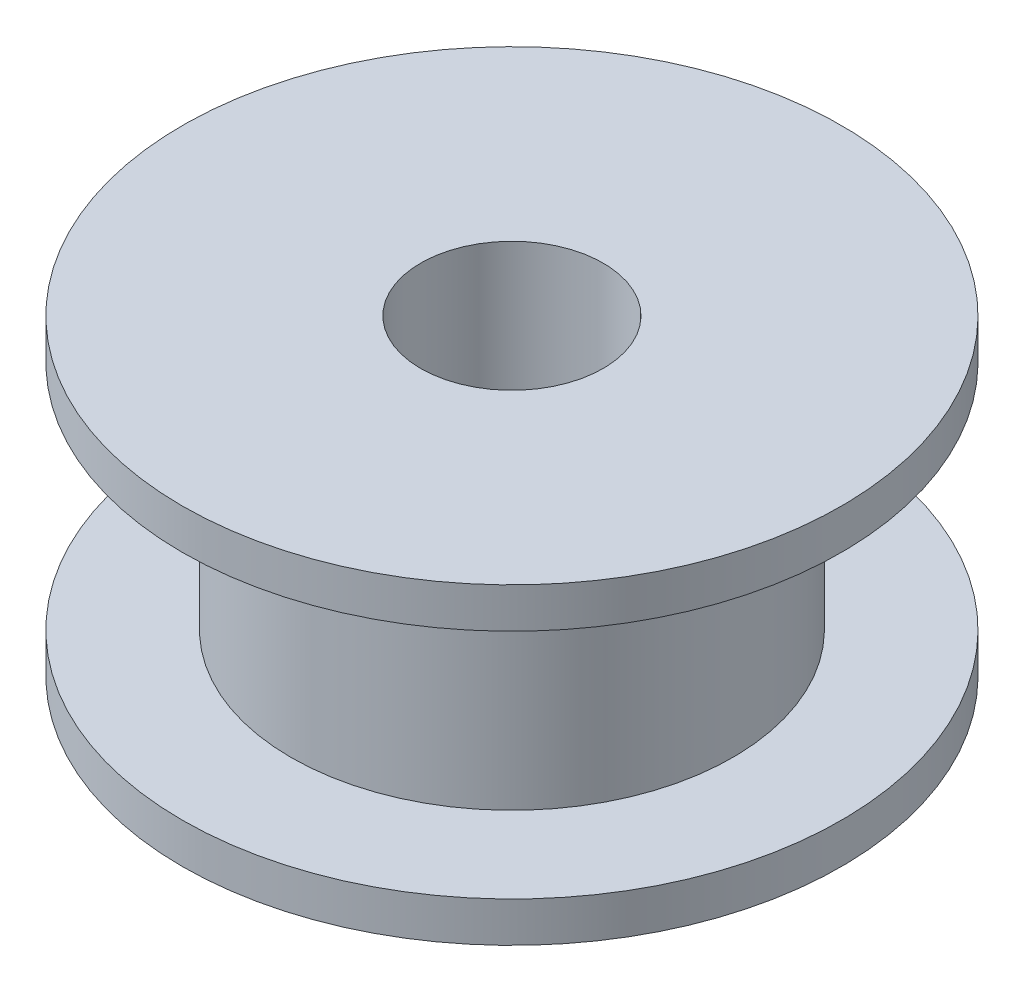
SolidWorks part; units mm, degrees
ref_plane "Front" through (0, 0, 0) normal (0, 0, 1) x (1, 0, 0)
ref_plane "Top" through (0, 0, 0) normal (0, 1, 0) x (1, 0, 0)
ref_plane "Right" through (0, 0, 0) normal (1, 0, 0) x (0, 0, -1)
sketch "Sketch1" plane through (0, 0, 0) normal (0, 1, 0) x (1, 0, 0)
  circle A0 centre (0, 0) radius 9.025
  circle A1 centre (0, 0) radius 6.05
  dimension "D1" = 12.1
  dimension "D2" = 18.05
extrude "Boss-Extrude1" add sketch "Sketch1" along normal blind 6.35 contours A1 region at (0, 0, 0)
extrude "Boss-Extrude2" add sketch "Sketch1<3>" against normal blind 1.1 contours A1 | A0 A1 region at (-8.7697, 0, 0) region at (0, 0, 0)
sketch "Sketch1<3>" plane through (0, 0, 0) normal (0, 1, 0) x (1, 0, 0) same geometry as "Sketch1"
extrude "Boss-Extrude3" add sketch "Sketch1<4>" along normal blind 1.1 from offset 6.35 contours A1 | A0 A1 region at (-8.7697, 0, 0) region at (0, 0, 0)
sketch "Sketch1<4>" plane through (0, 0, 0) normal (0, 1, 0) x (1, 0, 0) same geometry as "Sketch1"
sketch "Sketch2" plane through (0, 7.45, 0) normal (0, 1, 0) x (1, 0, 0)
  circle A0 centre (0, 0) radius 2.5
  dimension "D1" = 5
extrude "Cut-Extrude1" cut sketch "Sketch2" against normal up to next
